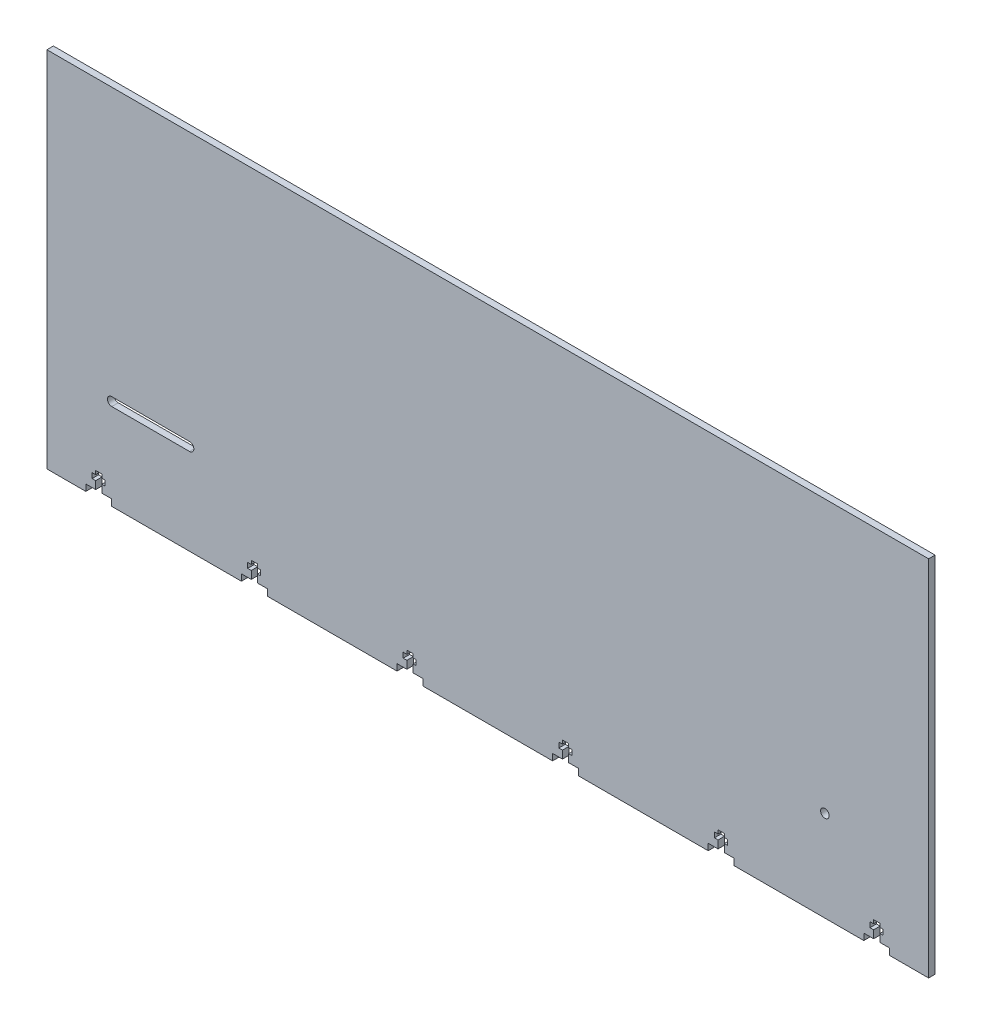
SolidWorks part; units mm, degrees
ref_plane "Front Plane" through (0, 0, 0) normal (0, 0, 1) x (1, 0, 0)
ref_plane "Top Plane" through (0, 0, 0) normal (0, 1, 0) x (1, 0, 0)
ref_plane "Right Plane" through (0, 0, 0) normal (1, 0, 0) x (0, 0, -1)
sketch "Sketch1" plane through (0, 0, 0) normal (0, 0, 1) x (1, 0, 0)
  line L1 (0, 0) -> (431.8, 0)
  line L2 (0, 0) -> (0, 177.8)
  line L3 (0, 177.8) -> (431.8, 177.8)
  line L4 (431.8, 0) -> (431.8, 177.8)
  dimension "D1" = 431.8
  dimension "D2" = 177.8
extrude "Boss-Extrude1" add sketch "Sketch1" along normal blind 3.175
sketch "Sketch2" plane through (0, 0, 3.175) normal (0, 0, 1) x (1, 0, 0)
  line L0 (31.75, 44.45) -> (69.85, 44.45) construction
  line L1 (31.75, 46.55) -> (69.85, 46.55)
  line L2 (31.75, 42.35) -> (69.85, 42.35)
  line L3 (0, 0) -> (431.8, 0) construction
  line L5 (0, 177.8) -> (0, 0) construction
  arc A0 (31.75, 46.55) -> (31.75, 42.35) centre (31.75, 44.45) ccw
  arc A1 (69.85, 42.35) -> (69.85, 46.55) centre (69.85, 44.45) ccw
  point P2 (50.8, 44.45)
  point P11 (0, 54.4037)
  dimension "D2" = 38.1
  dimension "D1" = 4.2
  dimension "D3" = 44.45
  dimension "D4" = 50.8
extrude "Cut-Extrude1" cut sketch "Sketch2" against normal blind 3.175
ref_plane "Plane1" through (215.9, 0, 0) normal (-1, 0, 0) x (0, 0, 1)
sketch "Sketch6" plane through (0, 0, 3.175) normal (0, 0, 1) x (1, 0, 0)
  line L2 (19.05, 0) -> (31.75, 0)
  line L3 (19.05, 0) -> (19.05, 3.175)
  line L4 (19.05, 3.175) -> (23.876, 3.175)
  line L5 (31.75, 0) -> (31.75, 3.175)
  line L6 (0, 177.8) -> (0, 0) construction
  line L7 (23.876, 3.175) -> (23.876, 6.985)
  line L8 (23.876, 11.303) -> (26.924, 11.303)
  line L9 (26.924, 3.175) -> (26.924, 6.985)
  line L10 (23.876, 9.525) -> (23.876, 11.303)
  line L11 (22.098, 9.525) -> (23.876, 9.525)
  line L12 (22.098, 9.525) -> (22.098, 6.985)
  line L13 (22.098, 6.985) -> (23.876, 6.985)
  line L14 (28.448, 9.525) -> (28.448, 6.985)
  line L15 (26.924, 9.525) -> (28.448, 9.525)
  line L16 (26.924, 9.525) -> (26.924, 11.303)
  line L17 (26.924, 6.985) -> (28.448, 6.985)
  line L18 (26.924, 3.175) -> (31.75, 3.175)
  line L19 (0, 0) -> (431.8, 0) construction
  point P8 (25.4, 11.303)
  dimension "D1" = 3.175
  dimension "D2" = 12.7
  dimension "D3" = 8.128
  dimension "D4" = 3.048
  dimension "D5" = 6.35
  dimension "D6" = 2.54
  dimension "D7" = 6.35
  dimension "D8" = 1.778
  dimension "D9" = 6.35
  dimension "D10" = 19.05
extrude "Cut-Extrude2" cut sketch "Sketch6" against normal blind 3.175
pattern_linear "LPattern1" count 6 spacing 76.2 along (1, 0, 0) of "Cut-Extrude2"
sketch "Sketch7" plane through (0, 0, 3.175) normal (0, 0, 1) x (1, 0, 0)
  line L0 (431.8, 0) -> (431.8, 177.8) construction
  line L2 (381, 44.45) -> (431.8, 44.45) construction
  circle A0 centre (381, 44.45) radius 2.1
  dimension "D1" = 4.2
  dimension "D2" = 50.8
  dimension "D3" = 44.45
extrude "Cut-Extrude3" cut sketch "Sketch7" against normal blind 3.175
